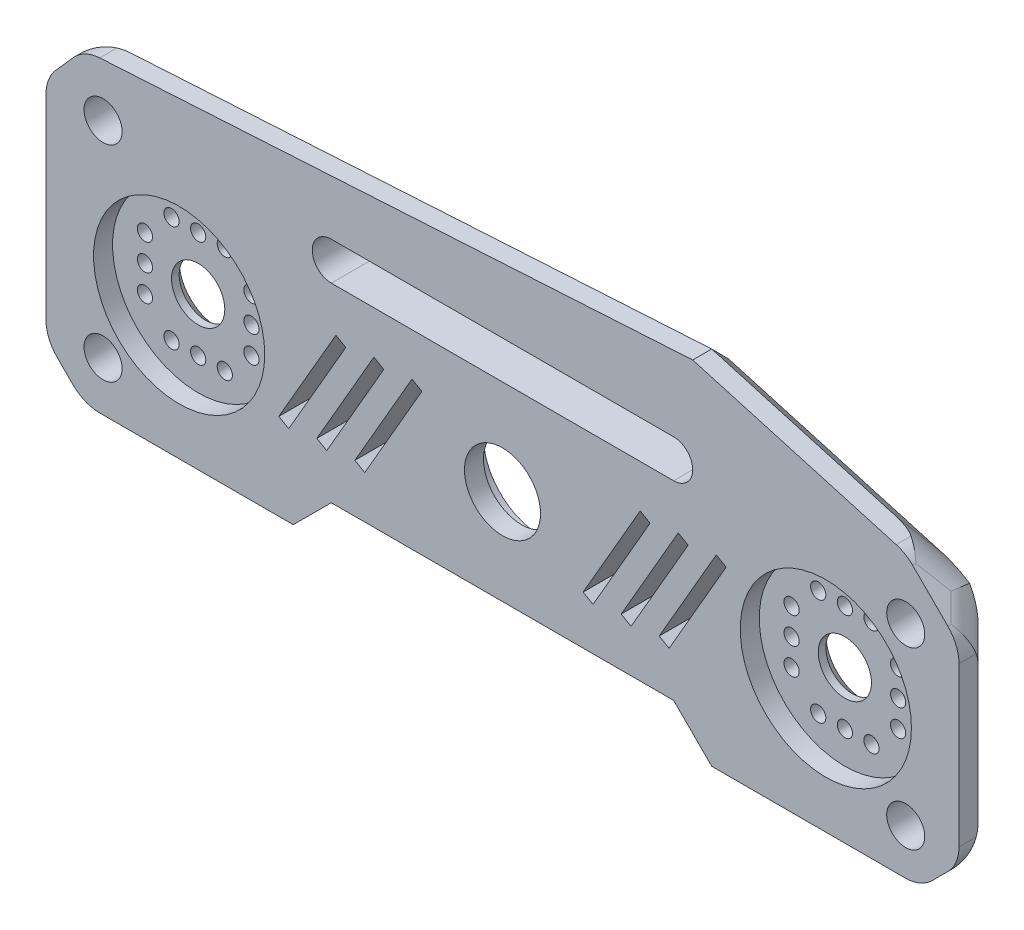
SolidWorks part; units mm, degrees
ref_plane "前视基准面" through (0, 0, 0) normal (0, 0, 1) x (1, 0, 0)
ref_plane "上视基准面" through (0, 0, 0) normal (0, 1, 0) x (1, 0, 0)
ref_plane "右视基准面" through (0, 0, 0) normal (1, 0, 0) x (0, 0, -1)
other "Configuration Table"
sketch "Sketch1" plane through (0, 0, 0) normal (0, 0, 1) x (1, 0, 0)
  line L0 (0, 0) -> (0, 12.5) construction
  line L1 (-42.5, -12.5) -> (42.5, -12.5)
  line L2 (-42.5, -12.5) -> (-42.5, 12.5)
  line L3 (-42.5, 12.5) -> (42.5, 12.5)
  line L4 (42.5, -12.5) -> (42.5, 12.5)
  line L5 (-42.5, -12.5) -> (42.5, 12.5) construction
  line L6 (-42.5, 12.5) -> (42.5, -12.5) construction
  line L7 (25, -17.5) -> (60, -17.5)
  line L8 (25, -17.5) -> (25, 17.5)
  line L9 (25, 17.5) -> (60, 17.5)
  line L10 (60, -17.5) -> (60, 17.5)
  line L11 (25, -17.5) -> (60, 17.5) construction
  line L12 (25, 17.5) -> (60, -17.5) construction
  line L13 (-25, 17.5) -> (-60, -17.5) construction
  line L14 (-25, -17.5) -> (-60, 17.5) construction
  line L15 (-60, -17.5) -> (-60, 17.5)
  line L16 (-25, 17.5) -> (-60, 17.5)
  line L17 (-25, -17.5) -> (-25, 17.5)
  line L18 (-25, -17.5) -> (-60, -17.5)
  line L19 (-42.5, -12.5) -> (-42.5, 12.5)
  point P0 (0, 0)
  point P6 (42.5, 0)
  point P17 (-42.5, 0)
  dimension "D1" = 85
  dimension "D2" = 25
  dimension "D3" = 35
  dimension "D4" = 35
extrude "Boss-Extrude1" add sketch "Sketch1" along normal blind 5 contours L1 L17 L3 L2 | L18 L17 L1 L2 L3 L16 L15 | L17 L1 L8 L3 | L8 L1 L4 L3 | L7 L10 L9 L8 L3 L4 L1 region at (-33.75, 0, 0) region at (-47.3611, 0, 0) region at (0, 0, 0) region at (33.75, 0, 0) region at (47.3611, 0, 0)
sketch "Sketch2" plane through (0, 0, 5) normal (0, 0, 1) x (1, 0, 0)
  line L0 (-60, 0) -> (60, 0) construction
  line L1 (-60, -17.5) -> (-60, 17.5) construction
  line L2 (60, -17.5) -> (60, 17.5) construction
  line L3 (-42.5, 17.5) -> (-42.5, -17.5) construction
  line L4 (-25, 17.5) -> (-60, 17.5) construction
  line L5 (-25, -17.5) -> (-60, -17.5) construction
  line L6 (42.5, 17.5) -> (42.5, -17.5) construction
  line L7 (25, 17.5) -> (60, 17.5) construction
  line L8 (25, -17.5) -> (60, -17.5) construction
  circle A0 centre (-42.5, 0) radius 11.25
  circle A1 centre (42.5, 0) radius 11.25
  point P18 (42.5, 0)
  point P19 (-42.5, 0)
  dimension "D1" = 22.5
  dimension "D2" = 22.5
extrude "Cut-Extrude1" cut sketch "Sketch2" against normal blind 2.5
sketch "Sketch3" plane through (0, 0, 2.5) normal (0, 0, 1) x (1, 0, 0)
  line L0 (42.5, 7) -> (46, 7) construction
  line L1 (42.5, 7) -> (42.5, 1.8094) construction
  line L2 (0, 0) -> (0, 12.5) construction
  line L3 (-25, 12.5) -> (25, 12.5) construction
  line L4 (-42.5, 7) -> (-42.5, 1.8094) construction
  line L5 (-42.5, 7) -> (-46, 7) construction
  line L6 (49.5, 0) -> (49.5, -3.5) construction
  line L7 (42.5, -7) -> (39, -7) construction
  line L8 (35.5, 0) -> (35.5, 3.5) construction
  circle A2 centre (42.5, 0) radius 7 construction
  circle A3 centre (42.5, 7) radius 1
  circle A4 centre (46, 7) radius 1
  circle A5 centre (39, 7) radius 1
  circle A6 centre (42.5, 0) radius 3.5
  circle A7 centre (-42.5, 0) radius 7 construction
  circle A8 centre (-42.5, 0) radius 3.5
  circle A9 centre (-39, 7) radius 1
  circle A10 centre (-46, 7) radius 1
  circle A11 centre (-42.5, 7) radius 1
  circle A12 centre (49.5, 0) radius 1
  circle A13 centre (49.5, -3.5) radius 1
  circle A14 centre (49.5, 3.5) radius 1
  circle A15 centre (42.5, -7) radius 1
  circle A16 centre (39, -7) radius 1
  circle A17 centre (46, -7) radius 1
  circle A18 centre (35.5, 0) radius 1
  circle A19 centre (35.5, 3.5) radius 1
  circle A20 centre (35.5, -3.5) radius 1
  circle A21 centre (-35.5, 3.5) radius 1
  circle A22 centre (-35.5, 0) radius 1
  circle A23 centre (-35.5, -3.5) radius 1
  circle A24 centre (-39, -7) radius 1
  circle A25 centre (-42.5, -7) radius 1
  circle A26 centre (-46, -7) radius 1
  circle A27 centre (-49.5, -3.5) radius 1
  circle A28 centre (-49.5, 0) radius 1
  circle A29 centre (-49.5, 3.5) radius 1
  point P49 (42.5, 0)
  point P66 (-42.5, 0)
  dimension "D1" = 4
  dimension "D2" = 4
  dimension "D3" = 14
  dimension "D4" = 2
  dimension "D5" = 2
  dimension "D7" = 7
  dimension "D6" = 3.5
extrude "Cut-Extrude2" cut sketch "Sketch3" against normal blind 5
sketch "Sketch4" plane through (0, 0, 5) normal (0, 0, 1) x (1, 0, 0)
  circle A0 centre (0, 0) radius 5
  dimension "D1" = 10
extrude "Cut-Extrude3" cut sketch "Sketch4" against normal blind 5
sketch "Sketch5" plane through (0, 0, 5) normal (0, 0, 1) x (1, 0, 0)
  line L0 (0, 0) -> (25, 0) construction
  line L1 (20.6005, -6.1202) -> (28.1005, 6.8702)
  line L2 (20.6005, -6.1202) -> (21.8995, -6.8702)
  line L3 (28.1005, 6.8702) -> (29.3995, 6.1202)
  line L4 (21.8995, -6.8702) -> (29.3995, 6.1202)
  line L5 (20.6005, -6.1202) -> (29.3995, 6.1202) construction
  line L6 (28.1005, 6.8702) -> (21.8995, -6.8702) construction
  line L7 (25, 0) -> (28.75, 6.4952) construction
  line L8 (16.8995, -6.8702) -> (24.3995, 6.1202)
  line L9 (15.6005, -6.1202) -> (16.8995, -6.8702)
  line L10 (23.1005, 6.8702) -> (24.3995, 6.1202)
  line L11 (15.6005, -6.1202) -> (23.1005, 6.8702)
  line L12 (11.8995, -6.8702) -> (19.3995, 6.1202)
  line L13 (10.6005, -6.1202) -> (11.8995, -6.8702)
  line L14 (18.1005, 6.8702) -> (19.3995, 6.1202)
  line L15 (10.6005, -6.1202) -> (18.1005, 6.8702)
  line L16 (6.8995, -6.8702) -> (14.3995, 6.1202)
  line L17 (5.6005, -6.1202) -> (6.8995, -6.8702)
  line L18 (13.1005, 6.8702) -> (14.3995, 6.1202)
  line L19 (5.6005, -6.1202) -> (13.1005, 6.8702)
  line L20 (1.8995, -6.8702) -> (9.3995, 6.1202)
  line L21 (0.6005, -6.1202) -> (1.8995, -6.8702)
  line L22 (8.1005, 6.8702) -> (9.3995, 6.1202)
  line L23 (0.6005, -6.1202) -> (8.1005, 6.8702)
  line L24 (-3.1005, -6.8702) -> (4.3995, 6.1202)
  line L25 (-4.3995, -6.1202) -> (-3.1005, -6.8702)
  line L26 (3.1005, 6.8702) -> (4.3995, 6.1202)
  line L27 (-4.3995, -6.1202) -> (3.1005, 6.8702)
  line L28 (-8.1005, -6.8702) -> (-0.6005, 6.1202)
  line L29 (-9.3995, -6.1202) -> (-8.1005, -6.8702)
  line L30 (-1.8995, 6.8702) -> (-0.6005, 6.1202)
  line L31 (-9.3995, -6.1202) -> (-1.8995, 6.8702)
  line L32 (-13.1005, -6.8702) -> (-5.6005, 6.1202)
  line L33 (-14.3995, -6.1202) -> (-13.1005, -6.8702)
  line L34 (-6.8995, 6.8702) -> (-5.6005, 6.1202)
  line L35 (-14.3995, -6.1202) -> (-6.8995, 6.8702)
  line L36 (-18.1005, -6.8702) -> (-10.6005, 6.1202)
  line L37 (-19.3995, -6.1202) -> (-18.1005, -6.8702)
  line L38 (-11.8995, 6.8702) -> (-10.6005, 6.1202)
  line L39 (-19.3995, -6.1202) -> (-11.8995, 6.8702)
  line L40 (-23.1005, -6.8702) -> (-15.6005, 6.1202)
  line L41 (-24.3995, -6.1202) -> (-23.1005, -6.8702)
  line L42 (-16.8995, 6.8702) -> (-15.6005, 6.1202)
  line L43 (-24.3995, -6.1202) -> (-16.8995, 6.8702)
  line L44 (-28.1005, -6.8702) -> (-20.6005, 6.1202)
  line L45 (-29.3995, -6.1202) -> (-28.1005, -6.8702)
  line L46 (-21.8995, 6.8702) -> (-20.6005, 6.1202)
  line L47 (-29.3995, -6.1202) -> (-21.8995, 6.8702)
  dimension "D1" = 120
  dimension "D2" = 25
  dimension "D3" = 1.5
  dimension "D4" = 15
  dimension "D5" = 11
extrude "Cut-Extrude4" cut sketch "Sketch5" against normal blind 5 contours L2 L4 L3 L1 | L11 L9 L8 L10 | L15 L13 L12 L14 | L39 L37 L36 L38 | L43 L41 L40 L42 | L47 L45 L44 L46 region at (25, 0, 5) region at (20, 0, 5) region at (15, 0, 5) region at (-15, 0, 5) region at (-20, 0, 5) region at (-25, 0, 5)
chamfer "Chamfer3" distance 1.5 angle 45 2 edges at (-39, 0, 0) (46, 0, 0)
sketch "Sketch7" plane through (0, 0, 0) normal (0, 0, -1) x (-1, 0, 0)
  line L12 (-60, 17.5) -> (-25, 27.5)
  line L13 (-25, 27.5) -> (60, 27.5)
  line L14 (60, 27.5) -> (60, 17.5)
  line L15 (-25, -17.5) -> (25, -17.5)
  line L16 (-25, 27.5) -> (60, 22.5)
  line L17 (60, 22.5) -> (60, 17.5)
  line L24 (25, -12.5) -> (25, -17.5)
  line L25 (25, -17.5) -> (60, -17.5)
  line L26 (60, -17.5) -> (60, 17.5)
  line L27 (60, 17.5) -> (25, 17.5)
  line L28 (25, 17.5) -> (25, 12.5)
  line L29 (25, 12.5) -> (-25, 12.5)
  line L30 (-25, 12.5) -> (-25, 17.5)
  line L31 (-25, 17.5) -> (-60, 17.5)
  line L32 (-60, 17.5) -> (-60, -17.5)
  line L33 (-60, -17.5) -> (-25, -17.5)
  line L34 (-25, -17.5) -> (-25, -12.5)
  line L35 (-25, -12.5) -> (25, -12.5)
  line L36 (25, -12.5) -> (25, -17.5)
  line L39 (60, 17.5) -> (25, 17.5)
  line L40 (25, 17.5) -> (25, 12.5)
  line L41 (25, 12.5) -> (-25, 12.5)
  line L42 (-25, 12.5) -> (-25, 17.5)
  line L43 (-25, 17.5) -> (-60, 17.5)
  line L46 (-25, -17.5) -> (-25, -12.5)
  line L47 (-25, -12.5) -> (25, -12.5)
  dimension "D2" = 10
  dimension "D3" = 35
  dimension "D1" = 0
extrude "Boss-Extrude2" add sketch "Sketch7" against normal blind 5 contours L43 L42 L41 L40 L39 L14 L13 L12 region at (-1.6275, 19.7941, 0)
chamfer "Chamfer4" distance 2.5 angle 45 13 edges at (-60, 2.5, 0) (-42.5, -17.5, 0) (60, 0, 0) (42.5, 22.5, 0) (-25, -15, 0) (-25, -12.5, 2.5) (25, -12.5, 2.5) (0, -12.5, 0) (25, -15, 0) (42.5, -17.5, 0) (-25, -17.5, 2.5) (25, -17.5, 2.5) (-17.5, 25, 0)
sketch "Sketch8" plane through (0, 0, 5) normal (0, 0, 1) x (1, 0, 0)
  line L0 (0, 0) -> (0, 15) construction
  line L1 (-22.5, 15) -> (22.5, 15) construction
  line L2 (-22.5, 17.5) -> (22.5, 17.5)
  line L3 (-22.5, 12.5) -> (22.5, 12.5)
  arc A0 (-22.5, 17.5) -> (-22.5, 12.5) centre (-22.5, 15) ccw
  arc A1 (22.5, 12.5) -> (22.5, 17.5) centre (22.5, 15) ccw
  point P5 (0, 15)
  dimension "D1" = 45
  dimension "D2" = 5
  dimension "D3" = 15
extrude "Cut-Extrude11" cut sketch "Sketch8" against normal blind 5
sketch "Sketch10" plane through (0, 0, 5) normal (0, 0, 1) x (1, 0, 0)
  line L1 (-42.5, 0) -> (0, 0) construction
  line L2 (-60, -17.5) -> (-60, 22.5) construction
  line L3 (-60, 2.5) -> (-52.5, 2.5) construction
  line L6 (42.5, 0) -> (53, 0) construction
  line L7 (53, 0) -> (53, -11.5) construction
  line L8 (-52.5, -11) -> (-52.5, 2.5) construction
  circle A0 centre (-52.5, -11) radius 2.5
  circle A4 centre (53, -11.5) radius 2.5
  circle A5 centre (53, 11.5) radius 2.5
  circle A6 centre (-52.5, 16) radius 2.5
  point P7 (-60, 2.5)
  dimension "D1" = 5
  dimension "D4" = 5
  dimension "D2" = 7.5
  dimension "D5" = 10.5
  dimension "D6" = 11.5
  dimension "D7" = 13.5
extrude "Cut-Extrude13" cut sketch "Sketch10" against normal blind 5
chamfer "Chamfer5" distance 5 angle 45 4 edges at (-60, -17.5, 3.75) (60, -17.5, 3.75) (60, 17.5, 3.75) (-60, 22.5, 3.75) first distance on face at (-43.75, -17.5, 3.75) first distance on face at (43.75, -17.5, 3.75) first distance on face at (60, 0, 3.75) first distance on face at (-17.5, 25, 3.75)
fillet "Fillet1" radius 5 16 edges at (-58.75, -13.75, 1.25) (-56.25, -16.25, 1.25) (54.82, 17.68, 1.25) (58.75, 13.75, 1.25) (56.25, -16.25, 1.25) (58.75, -13.75, 1.25) (53, 19.5, 3.75) (60, 12.5, 3.75) (55, -17.5, 3.75) (60, -12.5, 3.75) (-55, -17.5, 3.75) (-60, -12.5, 3.75) (-60, 17.1783, 3.75) (-58.75, 18.5846, 1.25) (-56.1831, 21.4724, 1.25) (-55.0086, 22.7936, 3.75)
sketch "Sketch12" plane through (0, 0, 0) normal (0, 0, -1) x (-1, 0, 0)
  circle A0 centre (0, 0) radius 7.5
  dimension "D1" = 15
extrude "Cut-Extrude14" cut sketch "Sketch12" against normal blind 2.5
